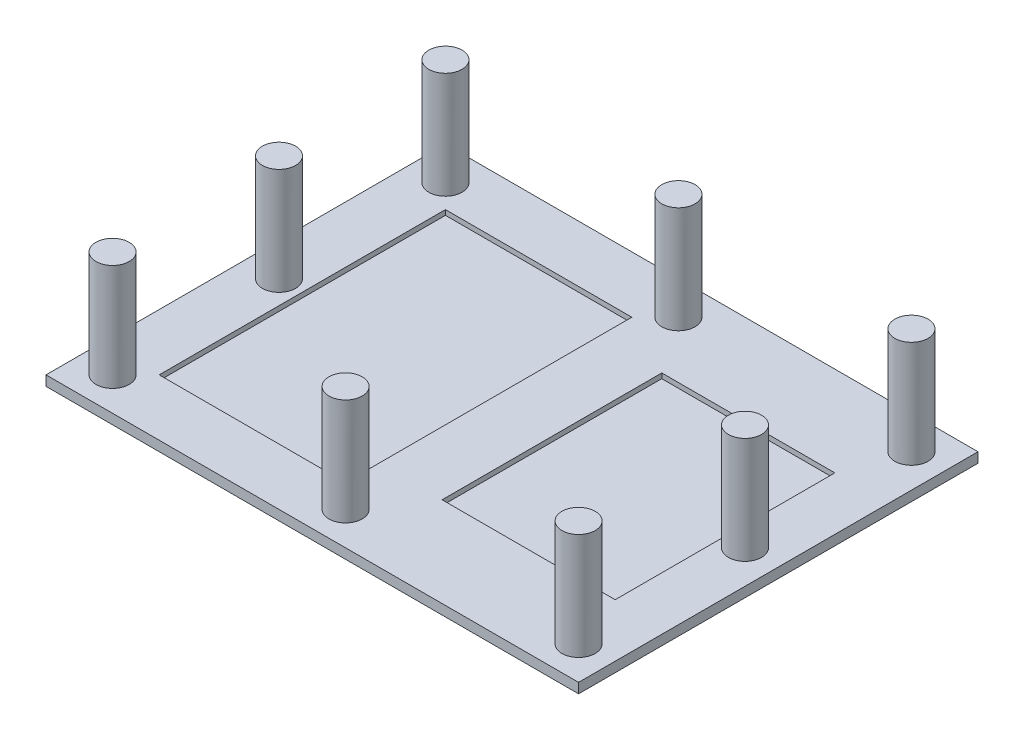
SolidWorks part; units mm, degrees
ref_plane "Front Plane" through (0, 0, 0) normal (0, 0, 1) x (1, 0, 0)
ref_plane "Top Plane" through (0, 0, 0) normal (0, 1, 0) x (1, 0, 0)
ref_plane "Right Plane" through (0, 0, 0) normal (1, 0, 0) x (0, 0, -1)
sketch "Sketch1" plane through (0, 0, 0) normal (0, 1, 0) x (1, 0, 0)
  line L1 (-80, -60) -> (80, -60)
  line L2 (-80, -60) -> (-80, 60)
  line L3 (-80, 60) -> (80, 60)
  line L4 (80, -60) -> (80, 60)
  line L5 (-80, -60) -> (80, 60) construction
  line L6 (-80, 60) -> (80, -60) construction
  point P0 (0, 0)
  dimension "D1" = 120
  dimension "D2" = 160
extrude "Boss-Extrude1" add sketch "Sketch1" along normal blind 3
sketch "Sketch2" plane through (0, 3, 0) normal (0, 1, 0) x (1, 0, 0)
  line L0 (0, 60) -> (0, 50) construction
  line L1 (80, 60) -> (-80, 60) construction
  line L2 (-80, -60) -> (80, -60) construction
  line L3 (80, 0) -> (70, 0) construction
  line L4 (80, -60) -> (80, 60) construction
  line L5 (-80, 0) -> (-70, 0) construction
  line L6 (-80, 60) -> (-80, -60) construction
  line L7 (-80, 60) -> (-70, 60) construction
  line L8 (-70, 60) -> (-70, 50) construction
  line L9 (-80, -60) -> (-70, -60) construction
  line L10 (-70, -60) -> (-70, -50) construction
  line L11 (80, 60) -> (70, 60) construction
  line L12 (70, 60) -> (70, 50) construction
  line L13 (80, -60) -> (70, -60) construction
  line L14 (70, -60) -> (70, -50) construction
  line L15 (0, -60) -> (0, -50) construction
  circle A0 centre (-70, 50) radius 5
  circle A1 centre (0, 50) radius 5
  circle A2 centre (70, 50) radius 5
  circle A3 centre (-70, 0) radius 5
  circle A4 centre (70, 0) radius 5
  circle A5 centre (-70, -50) radius 5
  circle A6 centre (0, -50) radius 5
  circle A7 centre (70, -50) radius 5
  dimension "D13" = 10
  dimension "D14" = 10
  dimension "D15" = 10
  dimension "D16" = 10
  dimension "D17" = 10
  dimension "D18" = 10
  dimension "D19" = 10
  dimension "D20" = 10
  dimension "D1" = 10
  dimension "D2" = 10
  dimension "D3" = 10
  dimension "D4" = 10
  dimension "D5" = 10
  dimension "D6" = 10
  dimension "D7" = 10
  dimension "D8" = 10
  dimension "D9" = 10
  dimension "D10" = 10
  dimension "D11" = 10
  dimension "D12" = 10
extrude "Boss-Extrude2" add sketch "Sketch2" along normal blind 32
sketch "Sketch3" plane through (0, 3, 0) normal (0, 1, 0) x (1, 0, 0)
  line L0 (80, 60) -> (-80, 60) construction
  line L1 (-63, -43) -> (-7, -43)
  line L2 (-63, -43) -> (-63, 43)
  line L3 (-63, 43) -> (-7, 43)
  line L4 (-7, -43) -> (-7, 43)
  line L6 (-80, 60) -> (-80, -60) construction
  dimension "D1" = 86
  dimension "D2" = 56
  dimension "D3" = 17
  dimension "D4" = 17
extrude "Cut-Extrude1" cut sketch "Sketch3" against normal blind 1.5 contours L2 L3 L4 L1
sketch "Sketch5" plane through (0, 3, 0) normal (0, 1, 0) x (1, 0, 0)
  line L0 (80, -60) -> (80, 60) construction
  line L1 (12, 33) -> (64, 33)
  line L2 (12, 33) -> (12, -33)
  line L3 (12, -33) -> (64, -33)
  line L4 (64, 33) -> (64, -33)
  line L5 (80, 60) -> (-80, 60) construction
  dimension "D1" = 52
  dimension "D2" = 66
  dimension "D3" = 16
  dimension "D4" = 27
extrude "Cut-Extrude2" cut sketch "Sketch5" against normal blind 1.5
